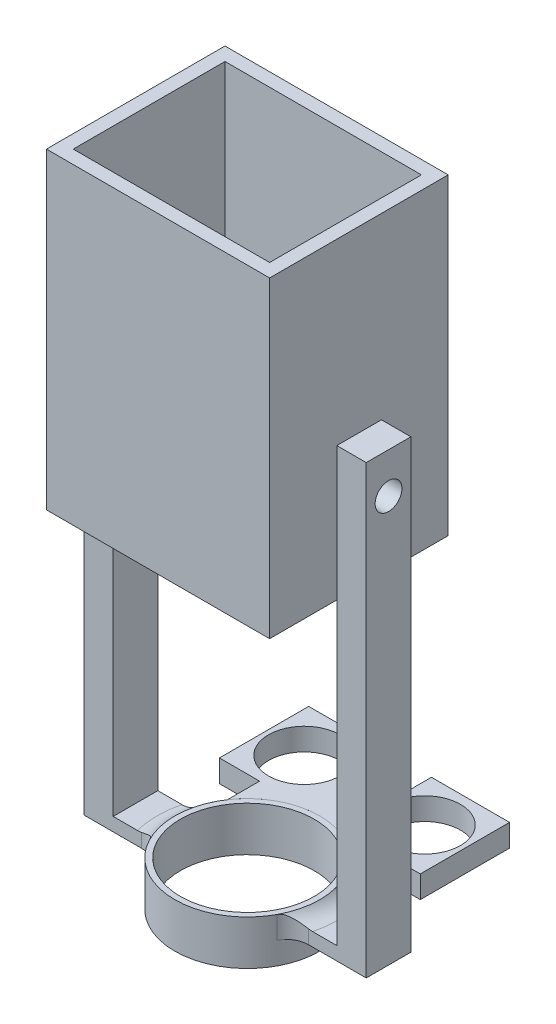
SolidWorks part; units mm, degrees
ref_plane "Front Plane" through (0, 0, 0) normal (0, 0, 1) x (1, 0, 0)
ref_plane "Top Plane" through (0, 0, 0) normal (0, 1, 0) x (1, 0, 0)
ref_plane "Right Plane" through (0, 0, 0) normal (1, 0, 0) x (0, 0, -1)
sketch "Sketch2" plane through (0, 0, 0) normal (0, 1, 0) x (1, 0, 0)
  line L0 (0, 15) -> (0, -15) construction
  line L1 (-15, 0) -> (15, 0) construction
  line L2 (-15, 0) -> (-15, 5) construction
  line L3 (-14.1421, 5) -> (-31.6421, 5)
  line L4 (-31.6421, 5) -> (-31.6421, -5)
  line L5 (-14.1421, -5) -> (-31.6421, -5)
  line L6 (14.1421, -5) -> (31.6421, -5)
  line L7 (31.6421, 5) -> (31.6421, -5)
  line L8 (14.1421, 5) -> (31.6421, 5)
  line L9 (0, 16.25) -> (22.5, 16.25)
  line L10 (22.5, 16.25) -> (22.5, 36.25)
  line L11 (22.5, 36.25) -> (5, 36.25)
  line L12 (-22.5, 36.25) -> (-22.5, 16.25)
  line L13 (-22.5, 16.25) -> (0, 16.25)
  line L14 (22.5, 26.25) -> (21.5, 26.25) construction
  line L20 (-5, 36.25) -> (-22.5, 36.25)
  line L21 (0, 31.25) -> (0, 16.25) construction
  line L22 (-5, 36.25) -> (-5, 31.25)
  line L23 (-5, 31.25) -> (5, 31.25)
  line L24 (5, 31.25) -> (5, 36.25)
  line L25 (13.5, 34.25) -> (13.5, 36.25) construction
  line L26 (13.5, 18.25) -> (13.5, 16.25) construction
  line L27 (-13.5, 26.25) -> (13.5, 26.25) construction
  line L28 (-13.5, 9.045) -> (-13.5, 16.25)
  line L29 (13.5, 16.25) -> (13.5, 9.045)
  line L30 (-16.25, 0) -> (-25.05, 0) construction
  line L31 (-25.05, 5) -> (-25.05, -5)
  line L32 (25.05, 5) -> (25.05, -5)
  circle A0 centre (0, 0) radius 15
  circle A1 centre (0, 0) radius 16.25
  circle A2 centre (13.5, 26.25) radius 8
  circle A3 centre (-13.5, 26.25) radius 8
  point P13 (-31.6421, 0)
  dimension "D1" = 30
  dimension "D2" = 17.5
  dimension "D4" = 32.5
  dimension "D8" = 1
  dimension "D9" = 16
  dimension "D3" = 5
  dimension "D5" = 5
  dimension "D6" = 20
  dimension "D7" = 45
  dimension "D10" = 17.5
  dimension "D11" = 8.8
extrude "Connector sleeve" add sketch "Sketch2" along normal blind 5 and the other way blind 5 contours L5 A1 L6 A0 | L8 A1 L3 A0 | L6 A1 L8 A0 | L3 A1 L5 A0 region at (-14.3253, 0, -6.9471) region at (-15.3497, 0, 0) region at (-14.8019, 0, 5.3291) region at (15.3497, 0, 0)
ref_plane "Plane2" through (0, 30, 0) normal (0, 1, 0) x (1, 0, 0)
sketch "Sketch3" plane through (0, 30, 0) normal (0, 1, 0) x (1, 0, 0)
  line L1 (-25, 20) -> (25, 20)
  line L2 (-25, 20) -> (-25, -20)
  line L3 (-25, -20) -> (25, -20)
  line L4 (25, 20) -> (25, -20)
  line L5 (-25, 20) -> (25, -20) construction
  line L6 (-25, -20) -> (25, 20) construction
  circle A0 centre (0, 0) radius 3
  point P0 (0, 0)
  dimension "D3" = 6
  dimension "D1" = 50
  dimension "D2" = 40
extrude "Motor casing" add sketch "Sketch3" along normal blind 70
shell "Shell4" thickness 3 removed face at (0, 100, 3) removed face at (0, 100, 0)
sketch "Sketch6" plane through (0, 33, 0) normal (0, 1, 0) x (1, 0, 0)
  circle A0 centre (0, 0) radius 15
  circle A1 centre (0, 0) radius 16
  dimension "D1" = 30
  dimension "D2" = 32
extrude "Motor sits here" add sketch "Sketch6" along normal blind 30
extrude "Sleeve-casing connector" add sketch "Sketch2<16>" along normal blind 3 contours A1 L3 L31 L5 | L31 L3 L4 L5 | A1 L6 L32 L8 | L8 L32 L6 L7 region at (-28.3461, 0, 0) region at (-20.5169, 0, 0) region at (20.5169, 0, 0) region at (28.3461, 0, 0)
sketch "Sketch2<16>" plane through (0, 0, 0) normal (0, 1, 0) x (1, 0, 0) same geometry as "Sketch2"
extrude "Sleeve-casing arms" add sketch "Sketch2<17>" along normal blind 100 contours L31 L3 L4 L5 | L8 L32 L6 L7 region at (-28.3461, 0, 0) region at (28.3461, 0, 0)
sketch "Sketch2<17>" plane through (0, 0, 0) normal (0, 1, 0) x (1, 0, 0) same geometry as "Sketch2"
extrude "Sensor holder" add sketch "Sketch2<10>" along normal blind 5 separate body contours L24 L23 L22 L20 L12 L13 L9 L10 L11 A2 A3 | A1 L13 L28 | A1 L29 L9 region at (-10.2927, 0, -14.2057) region at (0, 0, -25.4127) region at (10.2927, 0, -14.2057)
sketch "Sketch2<10>" plane through (0, 0, 0) normal (0, 1, 0) x (1, 0, 0) same geometry as "Sketch2"
fillet "Fillet2" radius 5 6 edges at (-15.4616, 1.5, -5) (-16.25, 3, 0) (-15.4616, 1.5, 5) (15.4616, 1.5, 5) (15.4616, 1.5, -5) (16.25, 3, 0)
ref_plane "Plane4" through (-31.6421, 0, 0) normal (-1, 0, 0) x (0, 0, 1)
sketch "Sketch8" plane through (-31.6421, 0, 0) normal (-1, 0, 0) x (0, 0, 1)
  line L0 (0, 100) -> (0, 91) construction
  line L1 (-5, 100) -> (5, 100) construction
  circle A0 centre (0, 91) radius 3
  dimension "D2" = 3
  dimension "D1" = 9
extrude "Cut-Extrude5" cut sketch "Sketch8" against normal through all both and the other way through all
move or copy body "Body-Move/Copy3" bodies to move or copy 104 copy no translate (0, 40, 0) parameters "D1"=0, "D2"=40, "D3"=0
